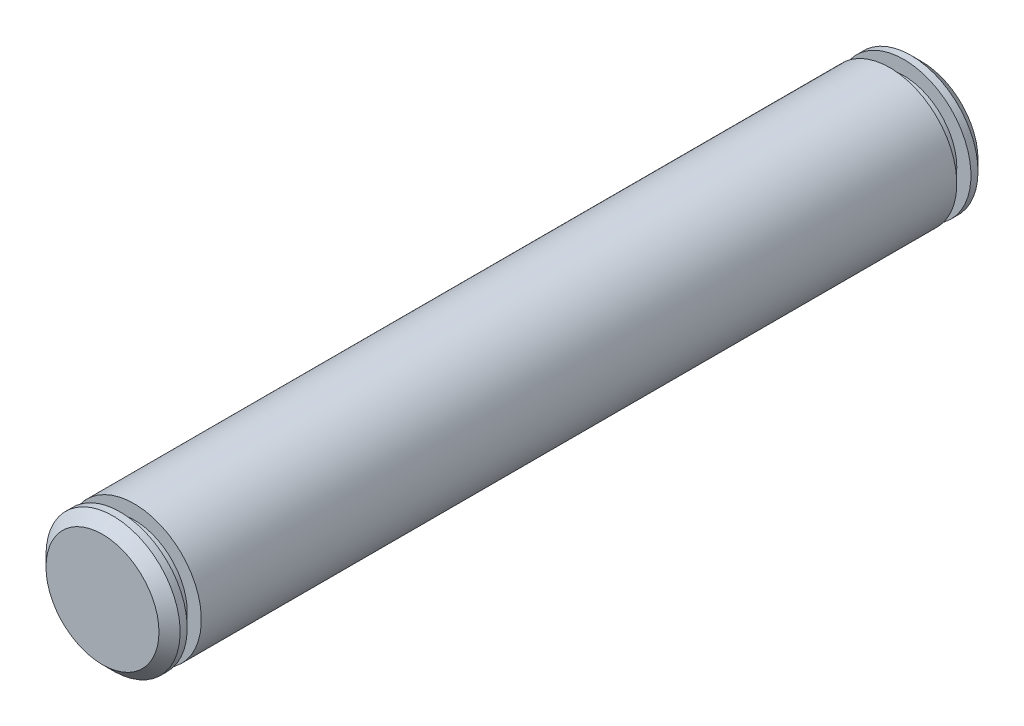
SolidWorks part; units mm, degrees
note: '?' marks a value the reader was unsure of.
ref_plane "Face" through (0, 0, 0) normal (0, 0, 1) x (1, 0, 0)
ref_plane "Dessus" through (0, 0, 0) normal (0, 1, 0) x (1, 0, 0)
ref_plane "Droite" through (0, 0, 0) normal (1, 0, 0) x (0, 0, -1)
sketch "Esquisse1" plane through (0, 0, 0) normal (0, 0, 1) x (1, 0, 0)
  circle A0 centre (0, 0) radius 9.5
  dimension "D1" = 19
extrude "Base-Extrusion" add sketch "Esquisse1" along normal blind 116
chamfer "Chanfrein1" distance 1.5 angle 45 2 edges at (9.5, 0, 0) (9.5, 0, 116)
ref_plane "Plan1" through (0, 0, 113.5) normal (0, 0, 1) x (1, 0, 0)
sketch "Esquisse2" plane through (0, 0, 113.5) normal (0, 0, 1) x (1, 0, 0)
  circle A0 centre (0, 0) radius 7.5
  circle A1 centre (0, 0) radius 12
  dimension "D1" = 15
  dimension "D2" = 24
extrude "Enlèv. mat.-Extru.1" cut sketch "Esquisse2" against normal blind 2
ref_axis "Axe1" through (0, 0, 166) along (0, 0, -1)?
pattern_linear "Répétition linéaire1" count 2 spacing 109 along (0, 0, -1) of "Enlèv. mat.-Extru.1"
